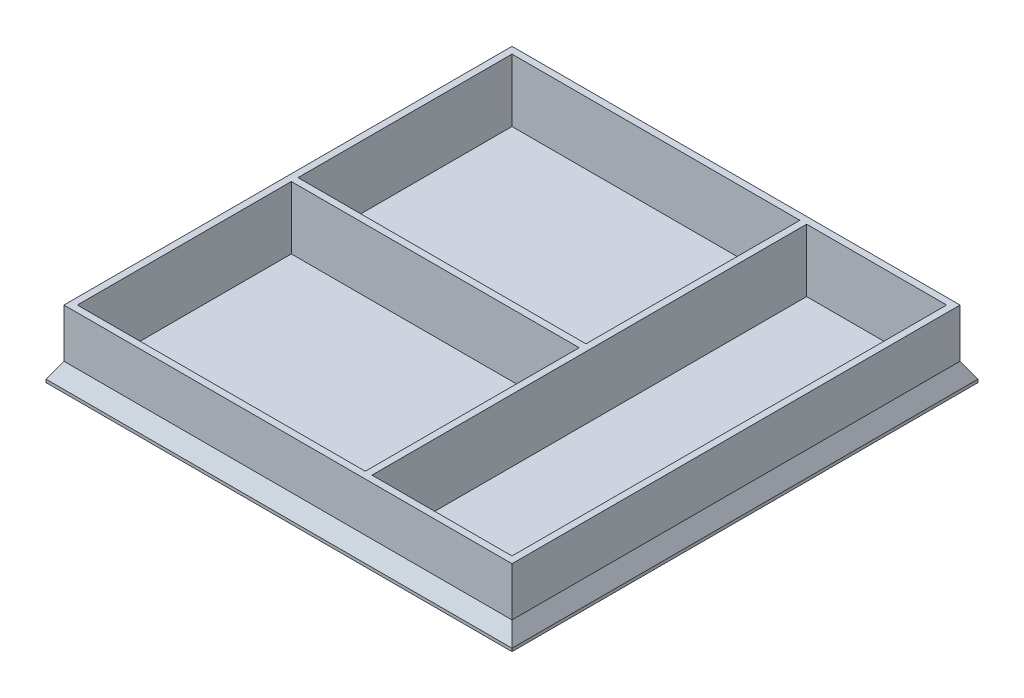
SolidWorks part; units mm, degrees
ref_plane "Přední rovina" through (0, 0, 0) normal (0, 0, 1) x (1, 0, 0)
ref_plane "Horní rovina" through (0, 0, 0) normal (0, 1, 0) x (1, 0, 0)
ref_plane "Pravá rovina" through (0, 0, 0) normal (1, 0, 0) x (0, 0, -1)
sketch "Skica1" plane through (0, 0, 0) normal (0, 1, 0) x (1, 0, 0)
  line L0 (-83.2, 83.2) -> (0, 0) construction
  line L1 (0, 0) -> (-83.2, 0)
  line L2 (0, 0) -> (0, 83.2)
  line L3 (0, 83.2) -> (-83.2, 83.2)
  line L4 (-83.2, 0) -> (-83.2, 83.2)
  line L5 (-83.2, 0) -> (0, 83.2) construction
  line L7 (-81.6, 81.6) -> (-1.6, 81.6)
  line L8 (-81.6, 81.6) -> (-81.6, 1.6)
  line L9 (-81.6, 1.6) -> (-1.6, 1.6)
  line L10 (-1.6, 81.6) -> (-1.6, 1.6)
  line L11 (-81.6, 81.6) -> (-1.6, 1.6) construction
  line L12 (-81.6, 1.6) -> (-1.6, 81.6) construction
  line L13 (-81.6, 41.6) -> (-1.6, 41.6) construction
  line L15 (-27.8, 80.4) -> (-2.8, 80.4)
  line L16 (-27.8, 80.4) -> (-27.8, 2.8)
  line L17 (-27.8, 2.8) -> (-2.8, 2.8)
  line L18 (-2.8, 80.4) -> (-2.8, 2.8)
  line L19 (-80.4, 80.4) -> (-29, 80.4)
  line L20 (-80.4, 80.4) -> (-80.4, 42.2)
  line L21 (-80.4, 42.2) -> (-29, 42.2)
  line L22 (-29, 80.4) -> (-29, 42.2)
  line L23 (-80.4, 41) -> (-29, 41)
  line L24 (-80.4, 41) -> (-80.4, 2.8)
  line L25 (-80.4, 2.8) -> (-29, 2.8)
  line L26 (-29, 41) -> (-29, 2.8)
  point P4 (-41.6, 41.6)
  dimension "D1" = 83.2
  dimension "D2" = 83.2
  dimension "D3" = 80
  dimension "D4" = 80
  dimension "D5" = 1.2
  dimension "D6" = 1.2
  dimension "D7" = 1.2
  dimension "D8" = 1.2
  dimension "D9" = 1.2
  dimension "D10" = 1.2
  dimension "D11" = 0.6
  dimension "D12" = 0.6
  dimension "D13" = 1.2
  dimension "D14" = 25
  dimension "D15" = 1.2
  dimension "D16" = 1.2
extrude "Přidat vysunutím1" add sketch "Skica1" along normal blind 0.8 contours L3 L4 L1 L2
extrude "Přidat vysunutím2" add sketch "Skica1<3>" along normal blind 12 contours L10 L7 L8 L9 L15 L18 L17 L16 L19 L22 L21 L20 L23 L26 L25 L24 region at (-40.8099, 0, -41.6)
sketch "Skica1<3>" plane through (0, 0, 0) normal (0, 1, 0) x (1, 0, 0) same geometry as "Skica1"
extrude "Přidat vysunutím3" add sketch "Skica1<4>" along normal blind 4 contours L4 L1 L2 L3 L7 L10 L9 L8 region at (-41.6, 0, -1.1766)
sketch "Skica1<4>" plane through (0, 0, 0) normal (0, 1, 0) x (1, 0, 0) same geometry as "Skica1"
chamfer "Zkosení2" distance 2 angle 60 4 edges at (-83.2, 4, -41.6) (-41.6, 4, -83.2) (0, 4, -41.6) (-41.6, 4, 0) first distance on face at (-41.6, 4, -41.6)
